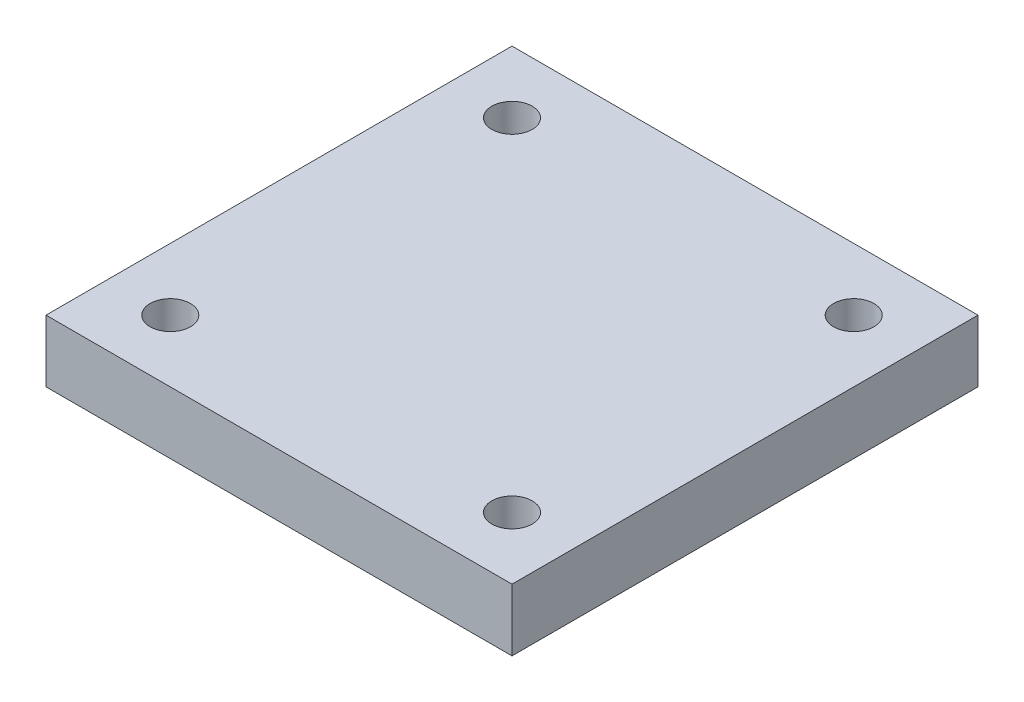
SolidWorks part; units mm, degrees
ref_plane "Front Plane" through (0, 0, 0) normal (0, 0, 1) x (1, 0, 0)
ref_plane "Top Plane" through (0, 0, 0) normal (0, 1, 0) x (1, 0, 0)
ref_plane "Right Plane" through (0, 0, 0) normal (1, 0, 0) x (0, 0, -1)
sketch "Sketch1" plane through (0, 0, 0) normal (0, 1, 0) x (1, 0, 0)
  line L1 (75, 75) -> (-75, 75)
  line L2 (75, 75) -> (75, -75)
  line L3 (75, -75) -> (-75, -75)
  line L4 (-75, 75) -> (-75, -75)
  line L5 (75, 75) -> (-75, -75) construction
  line L6 (75, -75) -> (-75, 75) construction
  point P0 (0, 0)
  dimension "D1" = 150
  dimension "D2" = 150
extrude "Boss-Extrude1" add sketch "Sketch1" along normal blind 20 contours L1 L4 L3 L2
sketch "Sketch2" plane through (0, 20, 0) normal (0, 1, 0) x (1, 0, 0)
  point P0 (55, 55)
  point P1 (55, -55)
  point P2 (-55, -55)
  point P3 (-55, 55)
  point P4 (0, 0)
  dimension "D1" = 110
  dimension "D2" = 55
  dimension "D3" = 55
  dimension "D4" = 55
hole_wizard "Ø12.0mm Dowel Hole1" positions "3DSketch1" profile "Sketch3" hole size "Ø12.0" standard "ANSI Metric" end condition up to next
sketch3d "3DSketch1"
  point P0 (55, 20, -55)
  point P3 (55, 20, 55)
  point P6 (-55, 20, 55)
  point P9 (-55, 20, -55)
sketch "Sketch3" plane through (55, 20, -55) normal (1, 0, 0) x (0, 0, 1)
  line L0 (0, 0) -> (0, 20)
  line L1 (0, 20) -> (6.5, 20)
  line L2 (6.5, 20) -> (6.5, 0)
  line L5 (6.5, 0) -> (0, 0)
  line L11 (0, -6.35) -> (0, 107.95) construction
  dimension "Thru Hole Dia." = 13
  dimension "Thru Hole Depth" = 20
equation "\"D3@Sketch2\"=\"D1@Sketch2\"/2"
equation "\"D2@Sketch2\"=\"D1@Sketch2\"/2"
equation "\"D4@Sketch2\"=\"D3@Sketch2\""
